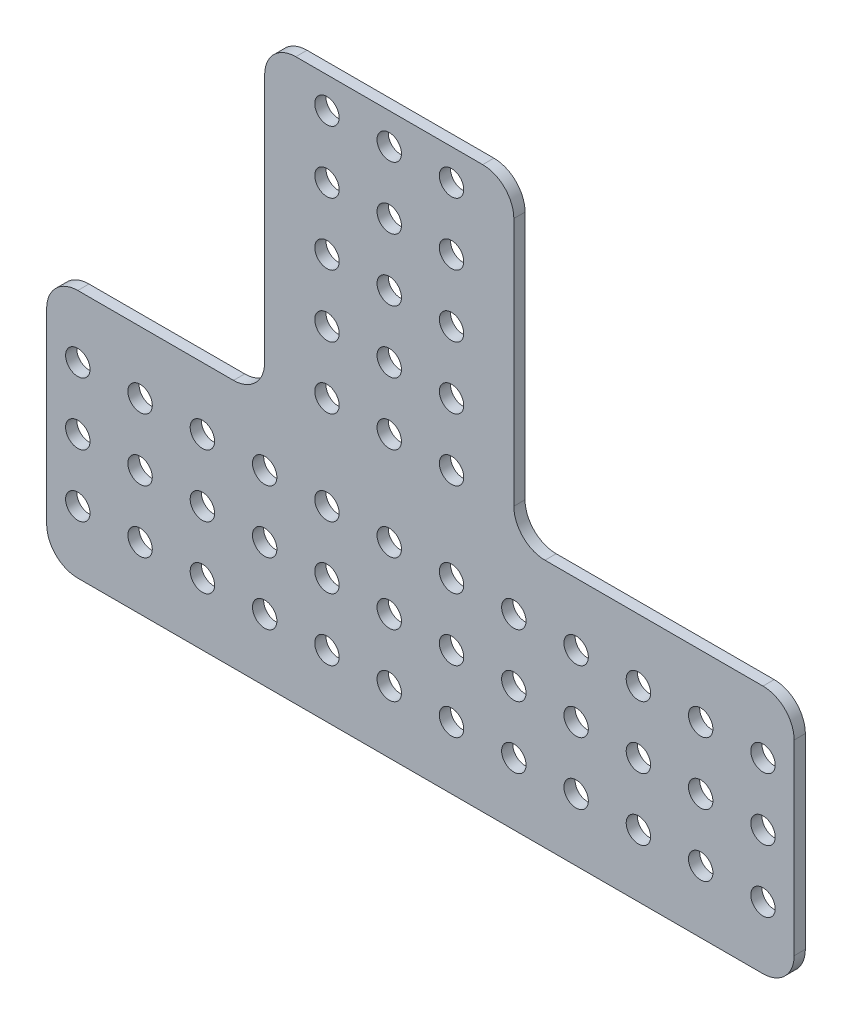
SolidWorks part; units mm, degrees
ref_plane "Front Plane" through (0, 0, 0) normal (0, 0, 1) x (1, 0, 0)
ref_plane "Top Plane" through (0, 0, 0) normal (0, 1, 0) x (1, 0, 0)
ref_plane "Right Plane" through (0, 0, 0) normal (1, 0, 0) x (0, 0, -1)
sketch "Sketch1" plane through (0, 0, 0) normal (0, 0, 1) x (1, 0, 0)
  line L0 (-258.2184, 188.8429) -> (-220.1184, 188.8429)
  line L1 (-213.7684, 182.4929) -> (-213.7684, 131.6929)
  line L2 (-207.4184, 125.3429) -> (-162.9684, 125.3429)
  line L3 (-156.6184, 118.9929) -> (-156.6184, 80.8929)
  line L4 (-162.9684, 74.5429) -> (-302.6684, 74.5429)
  line L5 (-309.0184, 80.8929) -> (-309.0184, 118.9929)
  line L6 (-302.6684, 125.3429) -> (-270.9184, 125.3429)
  line L8 (-264.5684, 125.3429) -> (-213.7684, 125.3429) construction
  line L9 (-213.7684, 811.1429) -> (-213.7684, 125.3429) construction
  line L10 (-302.6684, 112.6429) -> (-289.9684, 112.6429) construction
  line L11 (-302.6684, 112.6429) -> (-302.6684, 99.9429) construction
  line L12 (-226.4684, 131.6929) -> (-226.4684, 112.6429) construction
  line L13 (-264.5684, 131.6929) -> (-264.5684, 182.4929)
  arc A0 (-270.9184, 125.3429) -> (-264.5684, 131.6929) centre (-270.9184, 131.6929) ccw
  arc A1 (-309.0184, 118.9929) -> (-302.6684, 125.3429) centre (-302.6684, 118.9929) cw
  arc A2 (-302.6684, 74.5429) -> (-309.0184, 80.8929) centre (-302.6684, 80.8929) cw
  arc A3 (-156.6184, 80.8929) -> (-162.9684, 74.5429) centre (-162.9684, 80.8929) cw
  arc A4 (-162.9684, 125.3429) -> (-156.6184, 118.9929) centre (-162.9684, 118.9929) cw
  arc A5 (-213.7684, 131.6929) -> (-207.4184, 125.3429) centre (-207.4184, 131.6929) ccw
  arc A7 (-220.1184, 188.8429) -> (-213.7684, 182.4929) centre (-220.1184, 182.4929) cw
  circle A8 centre (-226.4684, 182.4929) radius 2.4892 construction
  circle A9 centre (-226.4684, 157.0929) radius 2.4892 construction
  circle A10 centre (-226.4684, 144.3929) radius 2.4892 construction
  circle A11 centre (-226.4684, 131.6929) radius 2.4892 construction
  circle A12 centre (-239.1684, 131.6929) radius 2.4892 construction
  circle A13 centre (-251.8684, 131.6929) radius 2.4892 construction
  circle A14 centre (-251.8684, 144.3929) radius 2.4892 construction
  circle A15 centre (-239.1684, 144.3929) radius 2.4892 construction
  circle A16 centre (-239.1684, 157.0929) radius 2.4892 construction
  circle A17 centre (-251.8684, 157.0929) radius 2.4892 construction
  circle A18 centre (-226.4684, 169.7929) radius 2.4892 construction
  circle A19 centre (-239.1684, 182.4929) radius 2.4892 construction
  circle A20 centre (-239.1684, 169.7929) radius 2.4892 construction
  circle A21 centre (-251.8684, 169.7929) radius 2.4892 construction
  circle A22 centre (-251.8684, 182.4929) radius 2.4892 construction
  circle A23 centre (-226.4684, 157.0929) radius 2.4892
  circle A24 centre (-226.4684, 144.3929) radius 2.4892
  circle A25 centre (-226.4684, 131.6929) radius 2.4892
  circle A26 centre (-239.1684, 131.6929) radius 2.4892
  circle A27 centre (-251.8684, 131.6929) radius 2.4892
  circle A28 centre (-251.8684, 144.3929) radius 2.4892
  circle A29 centre (-239.1684, 144.3929) radius 2.4892
  circle A30 centre (-239.1684, 157.0929) radius 2.4892
  circle A31 centre (-251.8684, 157.0929) radius 2.4892
  circle A32 centre (-226.4684, 169.7929) radius 2.4892
  circle A33 centre (-226.4684, 182.4929) radius 2.4892
  circle A34 centre (-239.1684, 182.4929) radius 2.4892
  circle A35 centre (-239.1684, 169.7929) radius 2.4892
  circle A36 centre (-251.8684, 169.7929) radius 2.4892
  circle A37 centre (-251.8684, 182.4929) radius 2.4892
  circle A38 centre (-302.6684, 112.6429) radius 2.4892
  circle A39 centre (-289.9684, 112.6429) radius 2.4892
  circle A40 centre (-277.2684, 112.6429) radius 2.4892
  circle A41 centre (-264.5684, 112.6429) radius 2.4892
  circle A42 centre (-251.8684, 112.6429) radius 2.4892
  circle A43 centre (-239.1684, 112.6429) radius 2.4892
  circle A44 centre (-226.4684, 112.6429) radius 2.4892
  circle A45 centre (-213.7684, 112.6429) radius 2.4892
  circle A46 centre (-201.0684, 112.6429) radius 2.4892
  circle A47 centre (-188.3684, 112.6429) radius 2.4892
  circle A48 centre (-175.6684, 112.6429) radius 2.4892
  circle A49 centre (-162.9684, 112.6429) radius 2.4892
  circle A50 centre (-289.9684, 99.9429) radius 2.4892
  circle A51 centre (-277.2684, 99.9429) radius 2.4892
  circle A52 centre (-264.5684, 99.9429) radius 2.4892
  circle A53 centre (-251.8684, 99.9429) radius 2.4892
  circle A54 centre (-239.1684, 99.9429) radius 2.4892
  circle A55 centre (-226.4684, 99.9429) radius 2.4892
  circle A56 centre (-213.7684, 99.9429) radius 2.4892
  circle A57 centre (-201.0684, 99.9429) radius 2.4892
  circle A58 centre (-188.3684, 99.9429) radius 2.4892
  circle A59 centre (-175.6684, 99.9429) radius 2.4892
  circle A60 centre (-162.9684, 99.9429) radius 2.4892
  circle A61 centre (-289.9684, 87.2429) radius 2.4892
  circle A62 centre (-277.2684, 87.2429) radius 2.4892
  circle A63 centre (-264.5684, 87.2429) radius 2.4892
  circle A64 centre (-251.8684, 87.2429) radius 2.4892
  circle A65 centre (-239.1684, 87.2429) radius 2.4892
  circle A66 centre (-226.4684, 87.2429) radius 2.4892
  circle A67 centre (-213.7684, 87.2429) radius 2.4892
  circle A68 centre (-201.0684, 87.2429) radius 2.4892
  circle A69 centre (-188.3684, 87.2429) radius 2.4892
  circle A70 centre (-175.6684, 87.2429) radius 2.4892
  circle A71 centre (-162.9684, 87.2429) radius 2.4892
  circle A72 centre (-302.6684, 99.9429) radius 2.4892
  circle A73 centre (-302.6684, 87.2429) radius 2.4892
  arc A75 (-264.5684, 182.4929) -> (-258.2184, 188.8429) centre (-258.2184, 182.4929) cw
  point P76 (0, 0)
  dimension "D2" = 6.35
  dimension "D6" = 12.7
  dimension "D8" = 4.9784
  dimension "D9" = 12
  dimension "D4" = 6.35
  dimension "D1" = 6.35
  dimension "D3" = 152.4
  dimension "D5" = 50.8
  dimension "D7" = 50.8
  dimension "D11" = 12.7
  dimension "D12" = 12.7
  dimension "D10" = 3
extrude "Boss-Extrude1" add sketch "Sketch1" along normal blind 2.286
